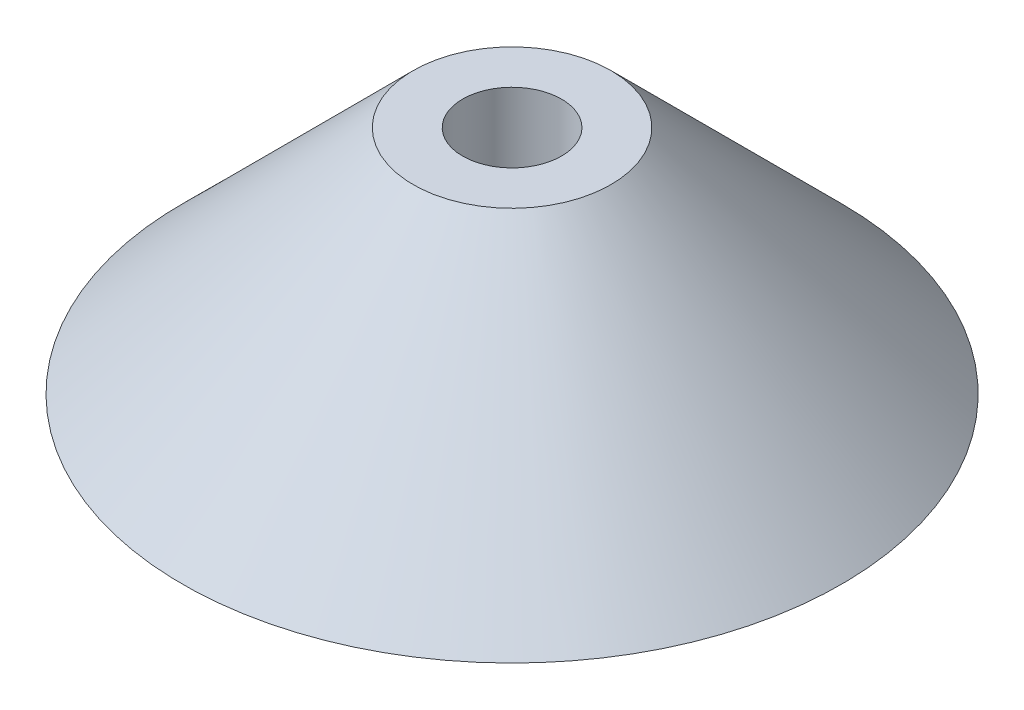
SolidWorks part; units mm, degrees
ref_plane "Front Plane" through (0, 0, 0) normal (0, 0, 1) x (1, 0, 0)
ref_plane "Top Plane" through (0, 0, 0) normal (0, 1, 0) x (1, 0, 0)
ref_plane "Right Plane" through (0, 0, 0) normal (1, 0, 0) x (0, 0, -1)
sketch "Sketch1" plane through (0, 0, 0) normal (0, 1, 0) x (1, 0, 0)
  circle A0 centre (0, 0) radius 10
extrude "Boss-Extrude1" add sketch "Sketch1" along normal blind 7
chamfer "Chamfer1" distance 7 angle 45 1 edges at (0, 7, 10)
sketch "Sketch2" plane through (0, 7, 0) normal (0, 1, 0) x (1, 0, 0)
  circle A0 centre (0, 0) radius 1.5
extrude "Cut-Extrude1" cut sketch "Sketch2" against normal through all
sketch "Sketch5" plane through (0, 0, 0) normal (0, 0, 1) x (1, 0, 0)
  line L0 (0, 0) -> (0, 10) construction
sketch "Sketch6" plane through (0, 0, 0) normal (0, 0, 1) x (1, 0, 0)
  line L0 (10, 0) -> (0, 10) construction
sketch "Sketch9" plane through (0, 7, 0) normal (0, 1, 0) x (1, 0, 0)
  line L0 (0, 0) -> (0, -3) construction
  circle A0 centre (0, 0) radius 3 construction
ref_plane "Plane1" through (0, 0, 0) normal (0, 0, 1) x (1, 0, 0)
